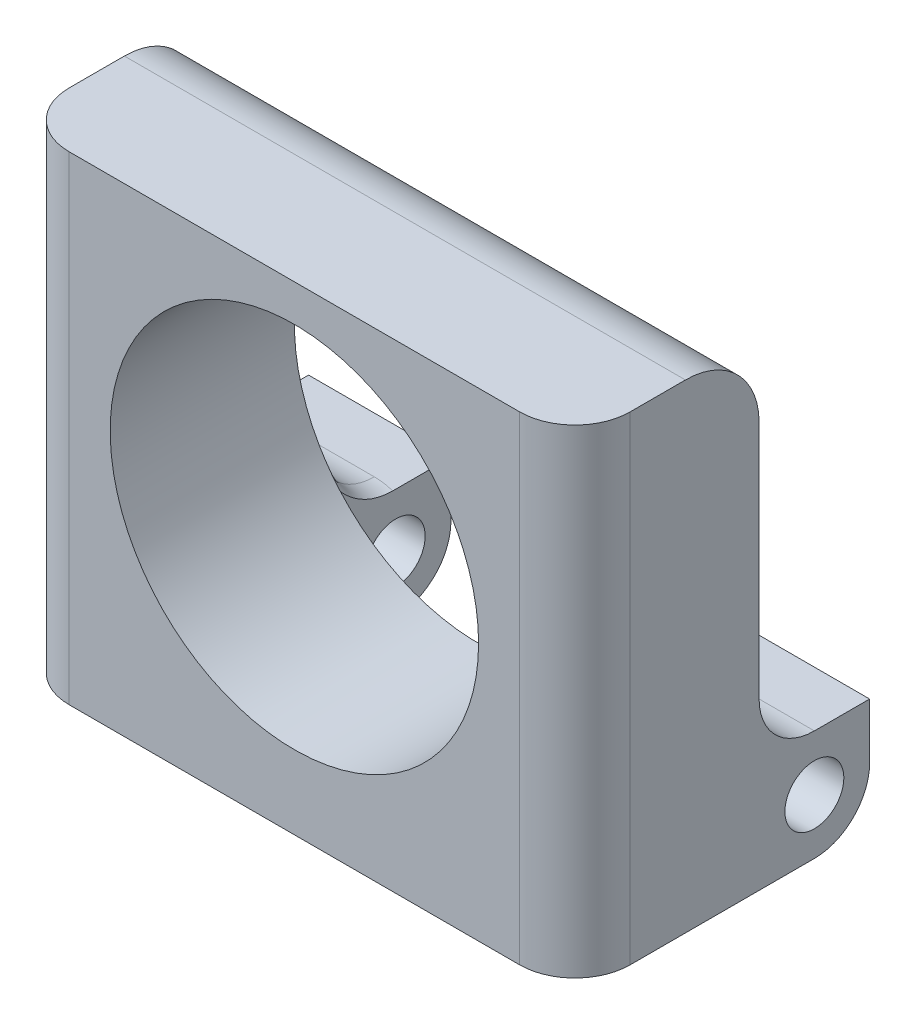
SolidWorks part; units mm, degrees
ref_plane "Front Plane" through (0, 0, 0) normal (0, 0, 1) x (1, 0, 0)
ref_plane "Top Plane" through (0, 0, 0) normal (0, 1, 0) x (1, 0, 0)
ref_plane "Right Plane" through (0, 0, 0) normal (1, 0, 0) x (0, 0, -1)
sketch "Sketch1" plane through (0, 0, 0) normal (0, 0, 1) x (1, 0, 0)
  line L0 (0, -14) -> (0, -10) construction
  line L1 (-15.2292, -14) -> (15.2292, -14)
  line L2 (-15.2292, -14) -> (-15.2292, 12)
  line L3 (-15.2292, 12) -> (15.2292, 12)
  line L4 (15.2292, -14) -> (15.2292, 12)
  line L5 (0, 10) -> (0, -10) construction
  circle A0 centre (0, 0) radius 10
  dimension "D1" = 20
  dimension "D2" = 4
  dimension "D3" = 26
extrude "Boss-Extrude1" add sketch "Sketch1" along normal blind 10
sketch "Sketch2" plane through (0, 0, 0) normal (0, 0, -1) x (-1, 0, 0)
  line L0 (15.2292, 12) -> (15.2292, -14) construction
  line L1 (-15.2292, -14) -> (15.2292, -14)
  line L2 (-15.2292, -14) -> (-15.2292, -8)
  line L3 (-15.2292, -8) -> (15.2292, -8)
  line L4 (15.2292, -14) -> (15.2292, -8)
  dimension "D1" = 6
extrude "Boss-Extrude2" add sketch "Sketch2" along normal blind 6
sketch "Sketch3" plane through (0, 0, -6) normal (0, 0, -1) x (-1, 0, 0)
  line L0 (0, -8) -> (0, -14) construction
  line L1 (-7.5, -8) -> (7.5, -8)
  line L2 (-7.5, -8) -> (-7.5, -14)
  line L3 (-7.5, -14) -> (7.5, -14)
  line L4 (7.5, -8) -> (7.5, -14)
  line L5 (15.2292, -8) -> (-15.2292, -8) construction
  line L6 (-15.2292, -14) -> (15.2292, -14) construction
  point P10 (0, -8)
  dimension "D1" = 15
  dimension "D2" = 6
extrude "Cut-Extrude1" cut sketch "Sketch3" against normal blind 6
fillet "Fillet1" radius 4 1 edges at (0, 12, 0)
sketch "Sketch4" plane through (15.2292, 0, 0) normal (1, 0, 0) x (0, 0, -1)
  line L0 (0, -8) -> (6, -14) construction
  circle A0 centre (3, -11) radius 1.6
  dimension "D1" = 3.2
extrude "Cut-Extrude2" cut sketch "Sketch4" against normal through all
fillet "Fillet2" radius 3 2 edges at (-11.3646, -14, -6) (11.3646, -14, -6)
fillet "Fillet3" radius 3 2 edges
fillet "Fillet4" radius 3 2 edges at (-15.2292, -1, 10) (15.2292, -1, 10)
